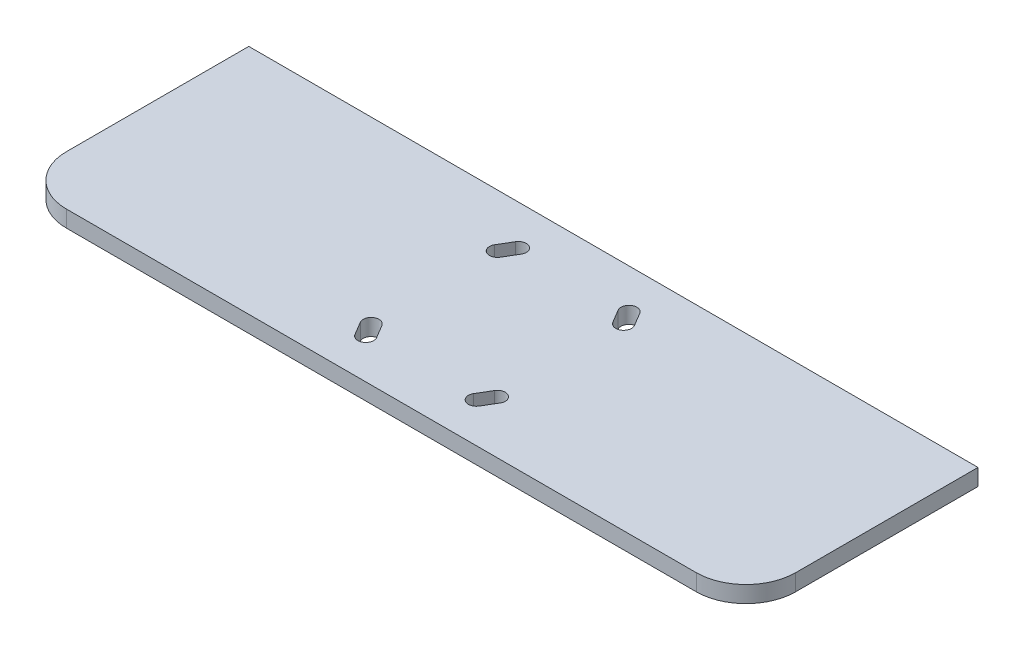
SolidWorks part; units mm, degrees
material "5052-H38, Rod (SS)"
ref_plane "Front Plane" through (0, 0, 0) normal (0, 0, 1) x (1, 0, 0)
ref_plane "Top Plane" through (0, 0, 0) normal (0, 1, 0) x (1, 0, 0)
ref_plane "Right Plane" through (0, 0, 0) normal (1, 0, 0) x (0, 0, -1)
sketch "Sketch1" plane through (0, 0, 0) normal (0, 1, 0) x (1, 0, 0)
  line L1 (-190, -70) -> (190, -70)
  line L2 (-220, -40) -> (-220, 70)
  line L3 (-220, 70) -> (220, 70)
  line L4 (220, -40) -> (220, 70)
  line L5 (-220, -70) -> (220, 70) construction
  line L6 (-220, 70) -> (220, -70) construction
  arc A0 (-190, -70) -> (-220, -40) centre (-190, -40) cw
  arc A1 (190, -70) -> (220, -40) centre (190, -40) ccw
  point P0 (0, 0)
  dimension "D3" = 30
  dimension "D4" = 30
  dimension "D1" = 440
  dimension "D2" = 140
extrude "Boss-Extrude1" add sketch "Sketch1" along normal blind 10
sketch "Sketch3" plane through (0, 10, 0) normal (0, 1, 0) x (1, 0, 0)
  line L0 (-2468.9744, -5833.1453) -> (-2476.9119, -5837.9078) construction
  line L1 (-2466.5241, -5837.2291) -> (-2474.4616, -5841.9916)
  line L2 (-2471.4247, -5829.0614) -> (-2479.3622, -5833.8239)
  line L3 (-2430.8744, -5871.2453) -> (-2430.8744, -5820.4453) construction
  line L4 (-2430.8744, -5871.2453) -> (-2373.7244, -5871.2453) construction
  line L5 (-2468.9744, -5909.3453) -> (-2476.9119, -5904.5828) construction
  line L6 (-2466.5241, -5905.2614) -> (-2474.4616, -5900.4989)
  line L7 (-2471.4247, -5913.4291) -> (-2479.3622, -5908.6666)
  line L8 (-2392.7744, -5833.1453) -> (-2384.8369, -5837.9078) construction
  line L9 (-2395.2247, -5837.2291) -> (-2387.2872, -5841.9916)
  line L10 (-2390.3241, -5829.0614) -> (-2382.3866, -5833.8239)
  line L11 (-2392.7744, -5909.3453) -> (-2384.8369, -5904.5828) construction
  line L12 (-2395.2247, -5905.2614) -> (-2387.2872, -5900.4989)
  line L13 (-2390.3241, -5913.4291) -> (-2382.3866, -5908.6666)
  line L14 (-38.1, -38.1) -> (-33.3375, -46.0375) construction
  line L15 (-34.0162, -35.6497) -> (-29.2537, -43.5872)
  line L16 (-42.1838, -40.5503) -> (-37.4213, -48.4878)
  line L17 (0, 42.0687) -> (0, -42.0687) construction
  line L19 (38.1, -38.1) -> (33.3375, -46.0375) construction
  line L20 (34.0162, -35.6497) -> (29.2537, -43.5872)
  line L21 (42.1838, -40.5503) -> (37.4213, -48.4878)
  line L22 (-38.1, 38.1) -> (-33.3375, 46.0375) construction
  line L23 (-34.0162, 35.6497) -> (-29.2537, 43.5872)
  line L24 (-42.1838, 40.5503) -> (-37.4213, 48.4878)
  line L25 (38.1, 38.1) -> (33.3375, 46.0375) construction
  line L26 (34.0162, 35.6497) -> (29.2537, 43.5872)
  line L27 (42.1838, 40.5503) -> (37.4213, 48.4878)
  line L28 (35.7187, 42.0687) -> (-35.7187, 42.0687) construction
  line L29 (-35.7187, 42.0687) -> (-35.7187, -42.0687) construction
  line L30 (-35.7187, -42.0687) -> (35.7187, -42.0687) construction
  line L31 (35.7187, -42.0687) -> (35.7187, 42.0687) construction
  arc A0 (-2466.5241, -5837.2291) -> (-2471.4247, -5829.0614) centre (-2468.9744, -5833.1453) ccw
  arc A1 (-2479.3622, -5833.8239) -> (-2474.4616, -5841.9916) centre (-2476.9119, -5837.9078) ccw
  arc A2 (-2466.5241, -5905.2614) -> (-2471.4247, -5913.4291) centre (-2468.9744, -5909.3453) cw
  arc A3 (-2479.3622, -5908.6666) -> (-2474.4616, -5900.4989) centre (-2476.9119, -5904.5828) cw
  arc A4 (-2395.2247, -5837.2291) -> (-2390.3241, -5829.0614) centre (-2392.7744, -5833.1453) cw
  arc A5 (-2382.3866, -5833.8239) -> (-2387.2872, -5841.9916) centre (-2384.8369, -5837.9078) cw
  arc A6 (-2395.2247, -5905.2614) -> (-2390.3241, -5913.4291) centre (-2392.7744, -5909.3453) ccw
  arc A7 (-2382.3866, -5908.6666) -> (-2387.2872, -5900.4989) centre (-2384.8369, -5904.5828) ccw
  arc A8 (-34.0162, -35.6497) -> (-42.1838, -40.5503) centre (-38.1, -38.1) ccw
  arc A9 (-37.4213, -48.4878) -> (-29.2537, -43.5872) centre (-33.3375, -46.0375) ccw
  arc A10 (34.0162, -35.6497) -> (42.1838, -40.5503) centre (38.1, -38.1) cw
  arc A11 (37.4213, -48.4878) -> (29.2537, -43.5872) centre (33.3375, -46.0375) cw
  arc A12 (-34.0162, 35.6497) -> (-42.1838, 40.5503) centre (-38.1, 38.1) cw
  arc A13 (-37.4213, 48.4878) -> (-29.2537, 43.5872) centre (-33.3375, 46.0375) cw
  arc A14 (34.0162, 35.6497) -> (42.1838, 40.5503) centre (38.1, 38.1) ccw
  arc A15 (37.4213, 48.4878) -> (29.2537, 43.5872) centre (33.3375, 46.0375) ccw
  point P2 (-2472.9432, -5835.5265)
  point P12 (-2472.9432, -5906.964)
  point P19 (-2388.8057, -5835.5265)
  point P26 (-2388.8057, -5906.964)
  point P33 (-35.7187, -42.0687)
  point P40 (0, 0)
  point P43 (35.7187, -42.0687)
  point P50 (-35.7187, 42.0687)
  point P57 (35.7187, 42.0687)
  dimension "D1" = 84.1375
  dimension "D2" = 71.4375
extrude "Cut-Extrude2" cut sketch "Sketch3" against normal through all
